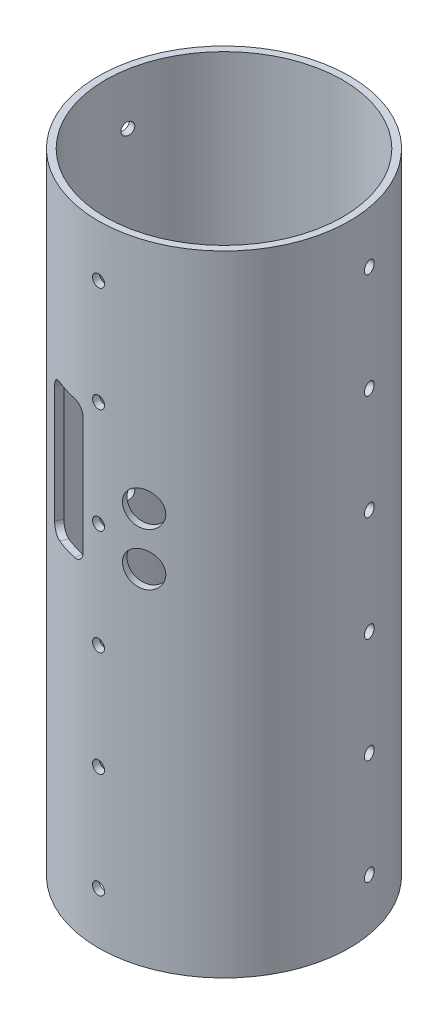
SolidWorks part; units mm, degrees
ref_plane "Front Plane" through (0, 0, 0) normal (0, 0, 1) x (1, 0, 0)
ref_plane "Top Plane" through (0, 0, 0) normal (0, 1, 0) x (1, 0, 0)
ref_plane "Right Plane" through (0, 0, 0) normal (1, 0, 0) x (0, 0, -1)
ref_plane "BULK LENGTH LIMIT" through (0, 183, 0) normal (0, 1, 0) x (1, 0, 0)
ref_axis "ROCKET AXIS" through (0, 146.5, 0) along (0, -1, 0)
sketch "Sketch1" plane through (0, 0, 0) normal (0, 1, 0) x (1, 0, 0)
  circle A0 centre (0, 0) radius 34.5
  circle A1 centre (0, 0) radius 36.5
  dimension "D1" = 69
  dimension "D2" = 2
extrude "BULK" add sketch "Sketch1" along normal up to surface (183 mm away) up to plane "BULK LENGTH LIMIT"
sketch "Sketch2" plane through (0, 0, 0) normal (0, 0, 1) x (1, 0, 0)
  line L0 (39.875, 183) -> (-39.875, 183) construction
  circle A0 centre (0, 15) radius 1.75
  circle A1 centre (0, 45.6) radius 1.75
  circle A2 centre (0, 76.2) radius 1.75
  circle A3 centre (0, 106.8) radius 1.75
  circle A4 centre (0, 137.4) radius 1.75
  circle A5 centre (0, 168) radius 1.75
  dimension "D2" = 3.5
  dimension "D1" = 15
  dimension "D4" = 15
  dimension "D3" = 6
extrude "FRONT HOLE CUTOUTS" cut sketch "Sketch2" along normal through all
pattern_circular "RIGHT HOLE CUTOUTS" count 2 every 100 about axis through (0, 146.5, 0) along (0, -1, 0) of "FRONT HOLE CUTOUTS"
mirror "LEFT HOLE CUTOUTS" about plane through (0, 0, 0) normal (1, 0, 0) of "RIGHT HOLE CUTOUTS"
ref_plane "UMBILICAL CUTOUT START PLANE" through (0, 0, 0) normal (0.9914, 0, 0.1305) x (0, -1, 0)
sketch "Sketch3" plane through (0, 0, 0) normal (0.9914, 0, 0.1305) x (0, -1, 0)
  line L0 (-146.5, 0) -> (-36.5, 0) construction
  line L1 (-94.02, -50) -> (-134.02, -50)
  line L2 (-94.02, -50) -> (-94.02, 0)
  line L3 (-94.02, 0) -> (-134.02, 0)
  line L4 (-134.02, -50) -> (-134.02, 0)
  ellipse E0 centre (-106.8, 0) end of major axis (-108.55, 0) minor radius 0.2284 construction
  dimension "D1" = 40
  dimension "D2" = 50
  dimension "D3" = 12.78
revolve "UMBILICAL CUT" cut sketch "Sketch3" angle 20 about axis through (0, 146.5, 0) along (0, -1, 0)
ref_plane "RBF MIDPLANE" through (0, 0, 0) normal (0.9511, 0, -0.309) x (0, -1, 0)
ref_plane "RBF TANGENT PLANE" through (11.2791, 0, 34.7136) normal (0.309, 0, 0.9511) x (0.9511, 0, -0.309)
sketch "Sketch4" plane through (11.2791, 0, 34.7136) normal (0.309, 0, 0.9511) x (0.9511, 0, -0.309)
  line L0 (0, -60.5) -> (0, 60.5) construction
  circle A0 centre (0, 115.3) radius 5
  circle A1 centre (0, 100.1) radius 5
  dimension "D2" = 10
  dimension "D1" = 15.2
  dimension "D3" = 52.7
extrude "RBF CUTOUTS" cut sketch "Sketch4" against normal up to next
fillet "Fillet1" radius 3 4 edges at (-4.6337, 134.02, 35.1963) (-16.3921, 134.02, 31.4889) (-4.6337, 94.02, 35.1963) (-16.3921, 94.02, 31.4889)
